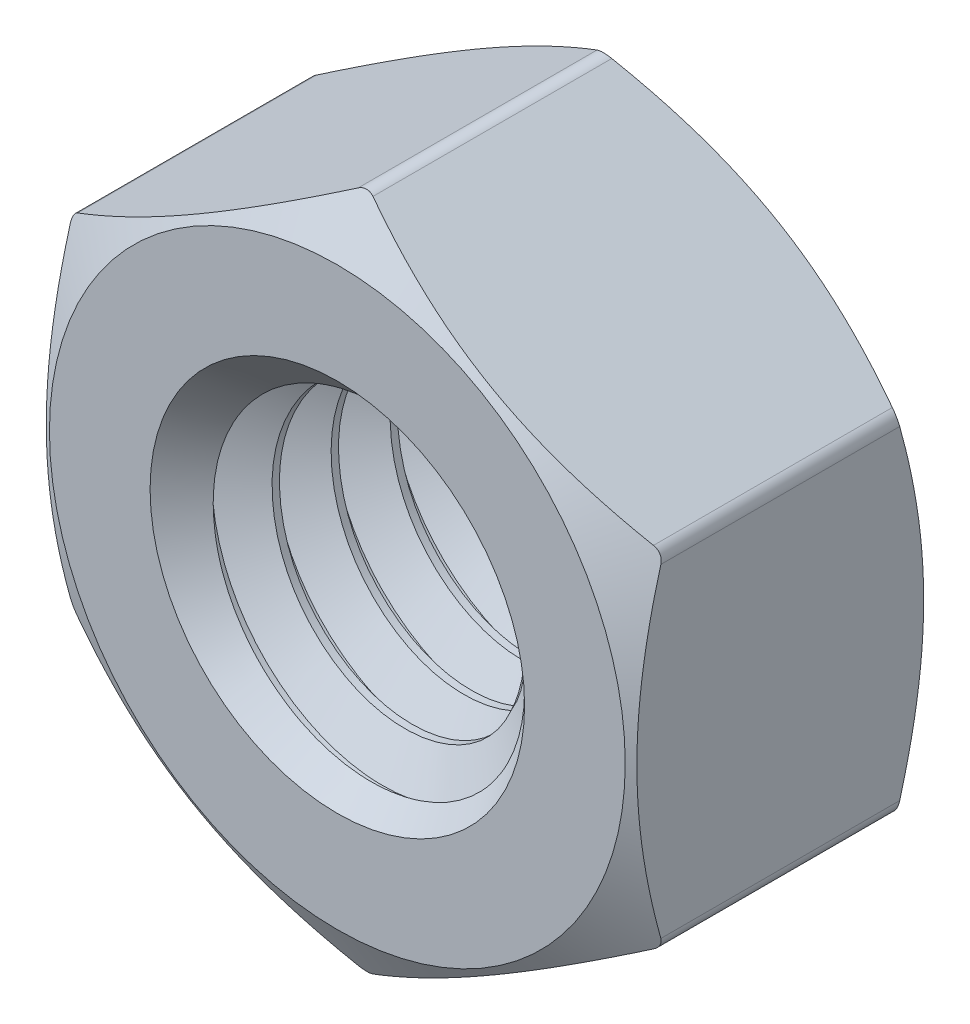
SolidWorks part; units mm, degrees
ref_plane "Front Plane" through (0, 0, 0) normal (0, 0, 1) x (1, 0, 0)
ref_plane "Top Plane" through (0, 0, 0) normal (0, 1, 0) x (1, 0, 0)
ref_plane "Right Plane" through (0, 0, 0) normal (1, 0, 0) x (0, 0, -1)
sketch "Sketch1" plane through (0, 0, 0) normal (1, 0, 0) x (0, 0, -1)
  line L0 (-2.5, 0) -> (2.5, 0) construction
  line L1 (-2.5, -5) -> (-2.5, 5) construction
  line L2 (2.5, -5) -> (2.5, 5) construction
  line L3 (-2.5, -3) -> (-2.5, 3) construction
  line L4 (-3.4375, 3.1083) -> (-2.9375, 2.2422) construction
  line L5 (-2.9375, 2.2422) -> (-2.4375, 3.1083) construction
  line L6 (-2.4375, 3.1083) -> (-3.4375, 3.1083) construction
  line L7 (-3.4063, 3.0541) -> (-2.4688, 3.0541) construction
  line L8 (-3.375, 3) -> (-2.5, 3) construction
  line L9 (-3, 2.3505) -> (-2.875, 2.3505) construction
  line L10 (-2.9375, 2.3505) -> (-2.9375, 2.2422) construction
  line L11 (-2.9375, 3.1083) -> (-2.9375, 3) construction
  line L12 (-2.5, 3.1708) -> (-2.3292, 3) construction
  point P4 (0, 0)
  point P7 (-2.5, 0)
  point P11 (2.5, 0)
  point P14 (-2.5, 0)
  point P26 (-2.9375, 3.0541)
  point P27 (-2.5, -3)
  dimension "Height" = 5
  dimension "Width" = 10
  dimension "Thread Size" = 6
  dimension "D1" = 60
  dimension "Thread Pitch" = 1
  dimension "D2" = 0.125
  dimension "D3" = 45
sketch "Sketch2" plane through (0, 0, 0) normal (0, 0, 1) x (1, 0, 0)
  line L1 (0, 5.7735) -> (-5, 2.8868)
  line L2 (-5, 2.8868) -> (-5, -2.8868)
  line L3 (-5, -2.8868) -> (0, -5.7735)
  line L4 (0, -5.7735) -> (5, -2.8868)
  line L5 (5, -2.8868) -> (5, 2.8868)
  line L6 (5, 2.8868) -> (0, 5.7735)
  circle A0 centre (0, 0) radius 5 construction
  circle A1 centre (0, 0) radius 3
extrude "Boss-Extrude1" add sketch "Sketch2" along normal up to vertex (2.5 mm away) and the other way up to vertex (2.5 mm away) up to point (0, -5, 2.5) other way up to point (0, -5, -2.5)
sketch "Sketch3" plane through (0, 0, 2.5) normal (0, 0, 1) x (1, 0, 0)
  circle A0 centre (0, 0) radius 4.875
  dimension "D1" = 9.75
extrude "Cut-Extrude1" cut sketch "Sketch3" against normal through all draft 60 flip side to cut
fillet "Fillet1" radius 0.25 6 edges at (5, -2.8868, -0.2594) (0, -5.7735, -0.2594) (-5, -2.8868, -0.2594) (-5, 2.8868, -0.2594) (5, 2.8868, -0.2594) (0, 5.7735, -0.2594)
sketch "Sketch8" plane through (0, 0, 2.5) normal (0, 0, 1) x (1, 0, 0)
  circle A0 centre (0, 0) radius 3.1708
extrude "Cut-Extrude4" cut sketch "Sketch8" against normal through all draft 45
mirror "Mirror1" about plane through (0, 0, 0) normal (0, 0, 1) of "Cut-Extrude4", "Cut-Extrude1"
sketch "Sketch4" plane through (0, 0, 0) normal (1, 0, 0) x (0, 0, -1)
  line L1 (-3.4063, 3.0541) -> (-3, 2.3505)
  line L2 (-3, 2.3505) -> (-2.875, 2.3505)
  line L3 (-2.875, 2.3505) -> (-2.4688, 3.0541)
  line L4 (-3.4063, 3.0541) -> (-2.4688, 3.0541) construction
  line L5 (-3.4063, 3.0541) -> (-2.4688, 3.0541)
sketch "Sketch5" plane through (0, 0, 2.5) normal (0, 0, 1) x (1, 0, 0)
  circle A0 centre (0, 0) radius 3 construction
  circle A1 centre (0, 0) radius 3
curve "Helix/Spiral1" pitch 1 height 6 radius 3 centre (0, 0, 2.5) axis (0, 0, -1) start towards (0, 1, 0)
sweep "Sweep1" add profiles "Sketch4" path "Helix/Spiral1"
sketch "Sketch6" plane through (0, 0, 2.5) normal (0, 0, 1) x (1, 0, 0)
  circle A0 centre (0, 0) radius 3.1708 construction
  circle A1 centre (0, 0) radius 3.1708
extrude "Cut-Extrude2" cut sketch "Sketch6" along normal through all and the other way through all draft 45
sketch "Sketch7" plane through (0, 0, -2.5) normal (0, 0, -1) x (-1, 0, 0)
  circle A1 centre (0, 0) radius 3.1708
  circle A2 centre (0, 0) radius 3.1708
  dimension "D1" = 0
extrude "Cut-Extrude3" cut sketch "Sketch7" along normal through all and the other way through all draft 45
equation "\"D2@Sketch1\"=\"Thread Pitch@Sketch1\"/8"
equation "\"D4@Helix/Spiral1\"=\"Thread Pitch@Sketch1\""
equation "\"D3@Helix/Spiral1\"=\"Height@Sketch1\"+\"Thread Pitch@Sketch1\""
equation "\"D1@Sketch3\"=\"Width@Sketch1\"*.975"
equation "\"D1@Fillet1\"=\"Width@Sketch1\"*.025"
